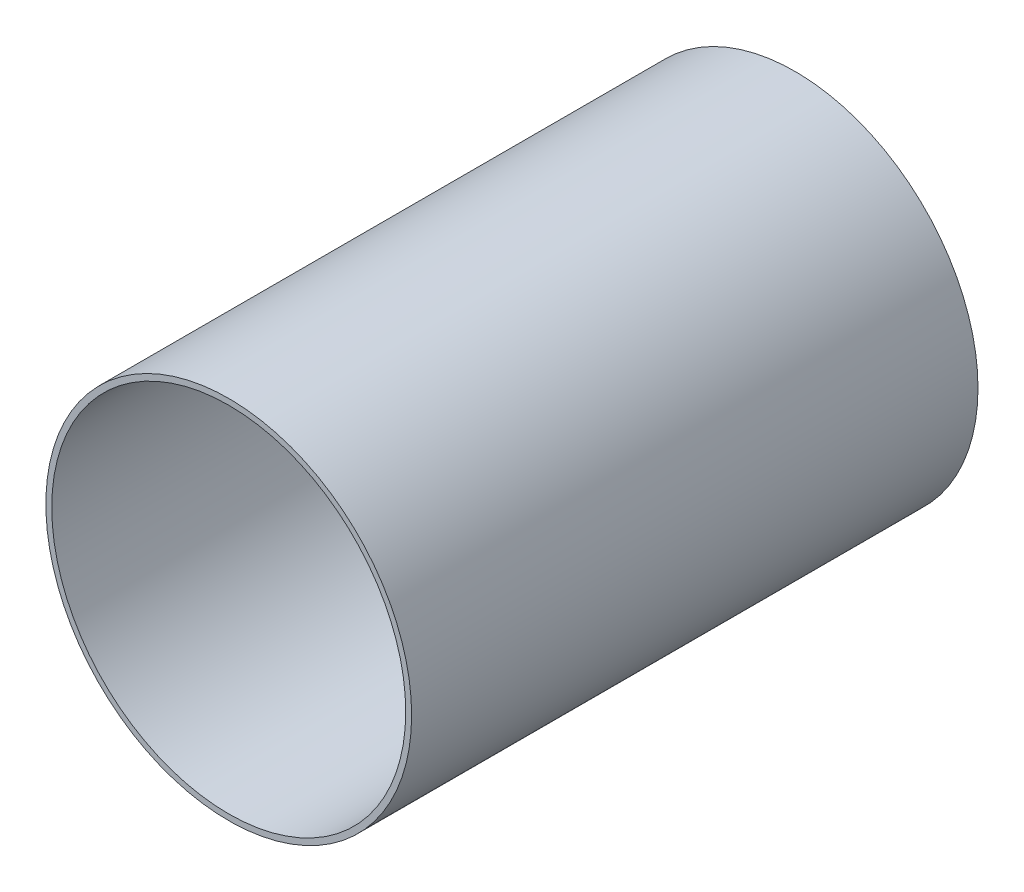
SolidWorks part; units mm, degrees
ref_plane "Front Plane" through (0, 0, 0) normal (0, 0, 1) x (1, 0, 0)
ref_plane "Top Plane" through (0, 0, 0) normal (0, 1, 0) x (1, 0, 0)
ref_plane "Right Plane" through (0, 0, 0) normal (1, 0, 0) x (0, 0, -1)
sketch "Sketch1" plane through (0, 0, 0) normal (0, 0, 1) x (1, 0, 0)
  circle A3 centre (0, 0) radius 15.5
  circle A4 centre (0, 0) radius 15
  circle A5 centre (0, 0) radius 15 construction
  dimension "D1" = 0.5
extrude "Boss-Extrude1" add sketch "Sketch1" against normal blind 48 contours A3 A4 region at (-15.0616, 0, 0)
